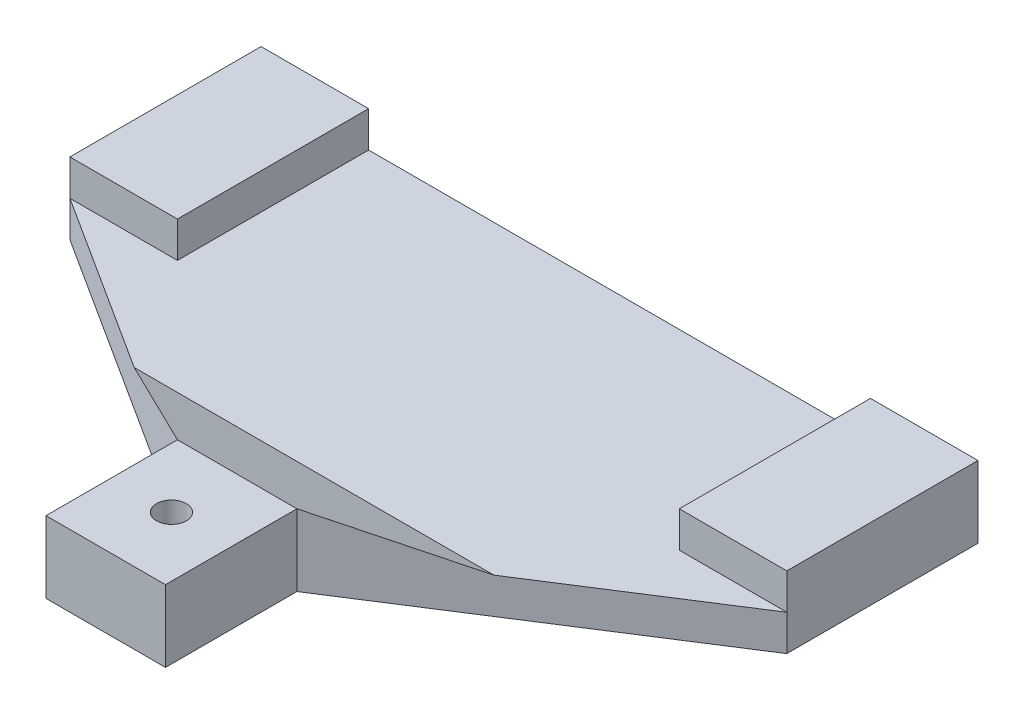
SolidWorks part; units mm, degrees
ref_plane "Plan de face" through (0, 0, 0) normal (0, 0, 1) x (1, 0, 0)
ref_plane "Plan de dessus" through (0, 0, 0) normal (0, 1, 0) x (1, 0, 0)
ref_plane "Plan de droite" through (0, 0, 0) normal (1, 0, 0) x (0, 0, -1)
sketch "Esquisse1" plane through (0, 0, 0) normal (0, 0, 1) x (1, 0, 0)
  line L1 (0, 0) -> (60, 0)
  line L2 (0, 0) -> (0, 6)
  line L3 (0, 6) -> (60, 6)
  line L4 (60, 0) -> (60, 6)
  dimension "D1" = 6
  dimension "D2" = 60
extrude "Boss.-Extru.1" add sketch "Esquisse1" along normal blind 60
sketch "Esquisse2" plane through (0, 0, 0) normal (0, 0, -1) x (-1, 0, 0)
  line L0 (-60, 6) -> (0, 6) construction
  line L1 (-60, 0) -> (-60, 6) construction
  line L2 (0, 6) -> (0, 0) construction
  circle A0 centre (-54, 3) radius 1.25
  circle A1 centre (-5.75, 3) radius 1.25
  dimension "D6" = 2.5
  dimension "D7" = 2.5
  dimension "D1" = 48.25
  dimension "D2" = 3
  dimension "D3" = 3
  dimension "D4" = 6
  dimension "D5" = 5.75
extrude "Enlèv. mat.-Extru.1" cut sketch "Esquisse2" against normal blind 15
sketch "Esquisse3" plane through (0, 6, 0) normal (0, 1, 0) x (1, 0, 0)
  line L0 (60, -60) -> (60, 0) construction
  line L1 (60, 0) -> (0, 0) construction
  circle A0 centre (30, -37.5) radius 1.25
  dimension "D1" = 2.5
  dimension "D2" = 30
  dimension "D3" = 37.5
extrude "Enlèv. mat.-Extru.2" cut sketch "Esquisse3" against normal blind 15
sketch "Esquisse4" plane through (0, 6, 0) normal (0, 1, 0) x (1, 0, 0)
  line L0 (0, -16) -> (9, -16)
  line L1 (0, -60) -> (0, 0) construction
  line L2 (9, -16) -> (9, 0)
  line L3 (60, 0) -> (0, 0) construction
  line L4 (9, 0) -> (51, 0)
  line L5 (51, 0) -> (51, -16)
  line L6 (51, -16) -> (60, -16)
  line L7 (60, -60) -> (60, 0) construction
  line L8 (60, -16) -> (60, -60)
  line L9 (60, -60) -> (0, -60)
  line L10 (0, -60) -> (0, -16)
  line L11 (25, -43) -> (35, -43)
  line L12 (35, -43) -> (35, -32)
  line L13 (35, -32) -> (25, -32)
  line L14 (25, -32) -> (25, -43)
  dimension "D1" = 9
  dimension "D2" = 9
  dimension "D3" = 16
  dimension "D4" = 16
  dimension "D5" = 17
  dimension "D6" = 32
  dimension "D7" = 25
  dimension "D8" = 25
extrude "Enlèv. mat.-Extru.3" cut sketch "Esquisse4" against normal blind 3
sketch "Esquisse5" plane through (0, 3, 0) normal (0, 1, 0) x (1, 0, 0)
  line L0 (60, -16) -> (35, -32)
  line L1 (35, -32) -> (35, -43)
  line L2 (35, -43) -> (25, -43)
  line L3 (25, -43) -> (25, -32)
  line L4 (25, -32) -> (0, -16)
  line L5 (0, -16) -> (-21.5949, -85.4755)
  line L6 (-21.5949, -85.4755) -> (75.4145, -69.9308)
  line L7 (75.4145, -69.9308) -> (60, -16)
extrude "Enlèv. mat.-Extru.4" cut sketch "Esquisse5" against normal blind 52
chamfer "Chanfrein1" distance 3 angle 65 1 edges at (30, 3, 32) first distance on face at (30, 4.5, 32)
